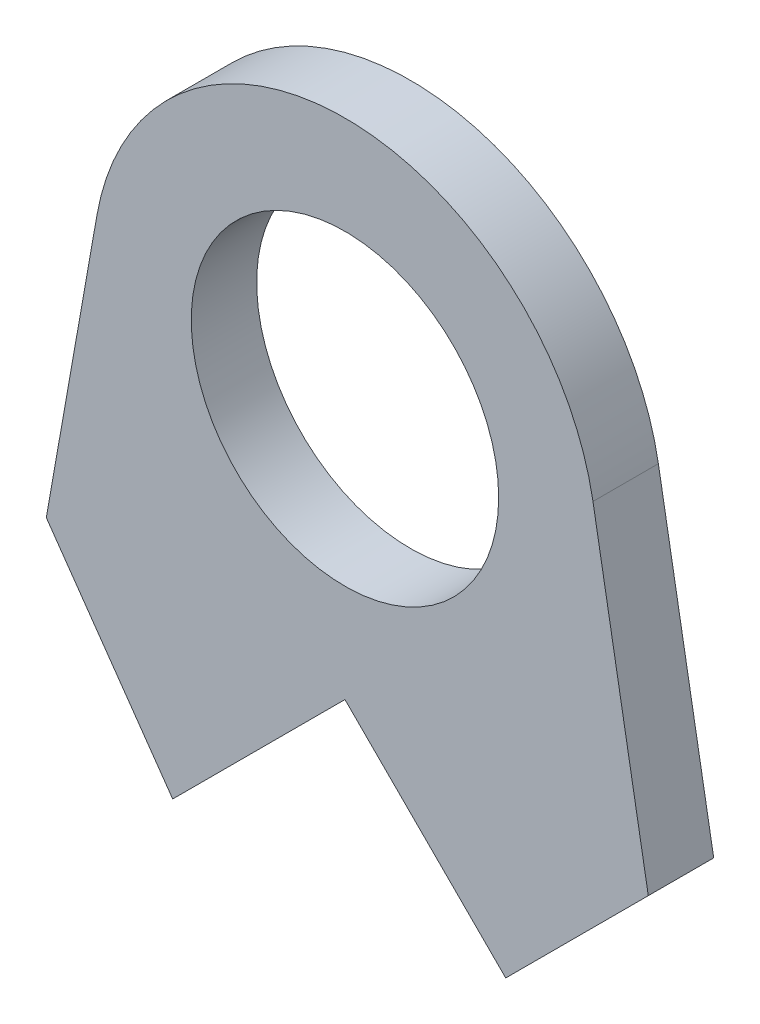
SolidWorks part; units mm, degrees
ref_plane "Plan de face" through (0, 0, 0) normal (0, 0, 1) x (1, 0, 0)
ref_plane "Plan de dessus" through (0, 0, 0) normal (0, 1, 0) x (1, 0, 0)
ref_plane "Plan de droite" through (0, 0, 0) normal (1, 0, 0) x (0, 0, -1)
sketch "Esquisse1" plane through (0, 0, 0) normal (0, 0, 1) x (1, 0, 0)
  line L0 (0, 0) -> (170, 0) construction
  line L1 (170, 0) -> (170, 5) construction
  line L2 (170, 5) -> (85, 487.059) construction
  line L3 (85, 5) -> (85, 303.8463) construction
  line L4 (85, 226.8463) -> (56.7157, 198.562)
  line L5 (0, 5) -> (0, 0) construction
  line L6 (0, 5) -> (170, 5) construction
  line L7 (56.7157, 198.562) -> (113.2843, 198.562) construction
  line L8 (170, 5) -> (85, 487.059) construction
  line L9 (0, 5) -> (85, 487.059) construction
  line L10 (170, 5) -> (122.9151, 272.0317) construction
  line L11 (47.0849, 272.0317) -> (0, 5) construction
  line L12 (170, 0) -> (170.8816, 0) construction
  line L13 (170.8816, 0) -> (170, 5) construction
  line L14 (85, 226.8463) -> (113.2843, 198.562)
  line L15 (56.7157, 198.562) -> (34.1302, 198.562)
  line L16 (113.2843, 198.562) -> (135.8698, 198.562)
  line L17 (47.0849, 272.0317) -> (34.1302, 198.562)
  line L18 (122.9151, 272.0317) -> (135.8698, 198.562)
  arc A0 (47.0849, 272.0317) -> (122.9151, 272.0317) centre (85, 265.3463) cw
  circle A1 centre (85, 265.3463) radius 23.5
  dimension "D6" = 15
  dimension "D7" = 38.5
  dimension "D8" = 47
  dimension "D5" = 40
  dimension "D1" = 5
  dimension "D2" = 170
  dimension "D3" = 80
  dimension "D4" = 45
extrude "Boss.-Extru.1" add sketch "Esquisse1" along normal blind 10
chamfer "Chanfrein1" distance 30 angle 45 2 edges at (34.1302, 198.562, 5) (135.8698, 198.562, 5) first distance on face at (40.6076, 235.2969, 5) first distance on face at (124.577, 198.562, 5)
